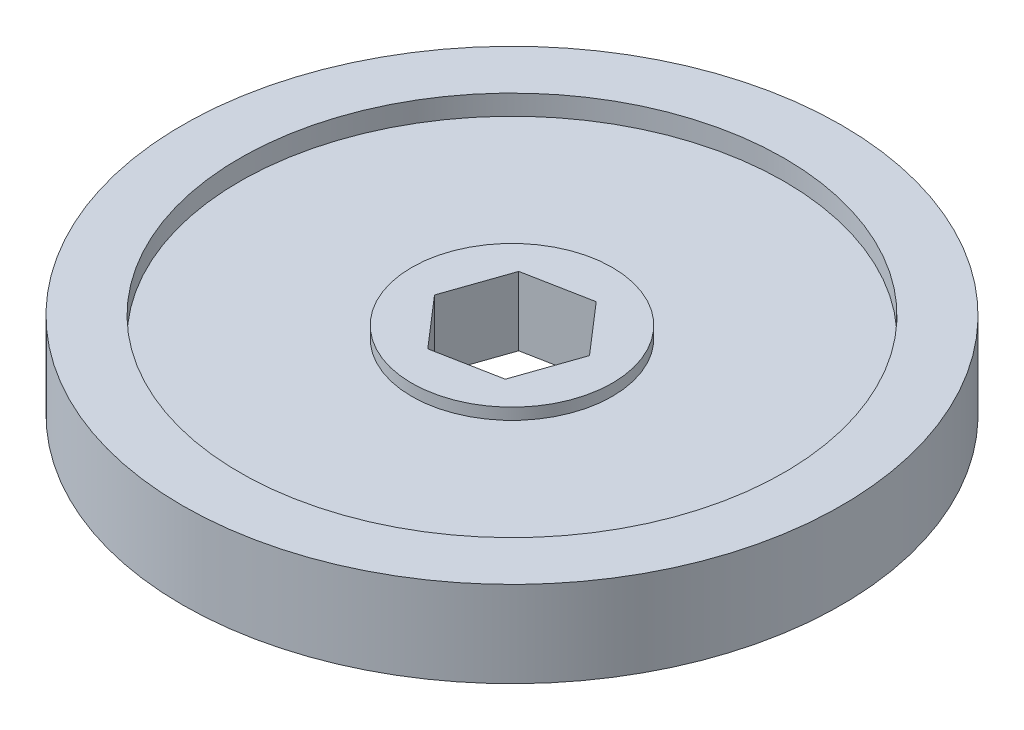
SolidWorks part; units mm, degrees
ref_plane "Front" through (0, 0, 0) normal (0, 0, 1) x (1, 0, 0)
ref_plane "Top" through (0, 0, 0) normal (0, 1, 0) x (1, 0, 0)
ref_plane "Right" through (0, 0, 0) normal (1, 0, 0) x (0, 0, -1)
sketch "Sketch1" plane through (0, 0, 0) normal (0, 1, 0) x (1, 0, 0)
  circle A0 centre (0, 0) radius 36.5125
  circle A2 centre (0, 0) radius 30.1625
  dimension "D1" = 73.025
  dimension "D2" = 6.35
extrude "Rim" add sketch "Sketch1" along normal blind 9.525
ref_plane "Mid_Plane" through (0, 4.7625, 0) normal (0, 1, 0) x (1, 0, 0)
sketch "Sketch2" plane through (0, 4.7625, 0) normal (0, 1, 0) x (1, 0, 0)
  line L1 (7.2008, 1.3829) -> (2.4028, 6.9275)
  line L2 (2.4028, 6.9275) -> (-4.798, 5.5446)
  line L3 (-4.798, 5.5446) -> (-7.2008, -1.3829)
  line L4 (-7.2008, -1.3829) -> (-2.4028, -6.9275)
  line L5 (-2.4028, -6.9275) -> (4.798, -5.5446)
  line L6 (4.798, -5.5446) -> (7.2008, 1.3829)
  circle A0 centre (0, 0) radius 30.1625 construction
  circle A1 centre (0, 0) radius 30.1625
  circle A2 centre (0, 0) radius 6.35 construction
extrude "Inner_Hub" add sketch "Sketch2" along normal blind 2.54 and the other way blind 2.54
sketch "Sketch3" plane through (0, 2.2225, 0) normal (0, -1, 0) x (1, 0, 0)
  line L6 (4.798, 5.5446) -> (-2.4028, 6.9275)
  line L7 (7.2008, -1.3829) -> (4.798, 5.5446)
  line L8 (2.4028, -6.9275) -> (7.2008, -1.3829)
  line L9 (-4.798, -5.5446) -> (2.4028, -6.9275)
  line L10 (-7.2008, 1.3829) -> (-4.798, -5.5446)
  line L11 (-2.4028, 6.9275) -> (-7.2008, 1.3829)
  line L12 (4.798, 5.5446) -> (-2.4028, 6.9275)
  line L13 (7.2008, -1.3829) -> (4.798, 5.5446)
  line L14 (2.4028, -6.9275) -> (7.2008, -1.3829)
  line L15 (-4.798, -5.5446) -> (2.4028, -6.9275)
  line L16 (-7.2008, 1.3829) -> (-4.798, -5.5446)
  line L17 (-2.4028, 6.9275) -> (-7.2008, 1.3829)
  circle A0 centre (0, 0) radius 11.1125
  dimension "D2" = 22.225
  dimension "D1" = 0
extrude "Hex_Step" add sketch "Sketch3" along normal blind 1.27
mirror "Mirror1" about plane through (0, 4.7625, 0) normal (0, 1, 0) of "Hex_Step"
ref_axis "Cen_Axis" through (0, 9.525, 0) along (0, -1, 0)
